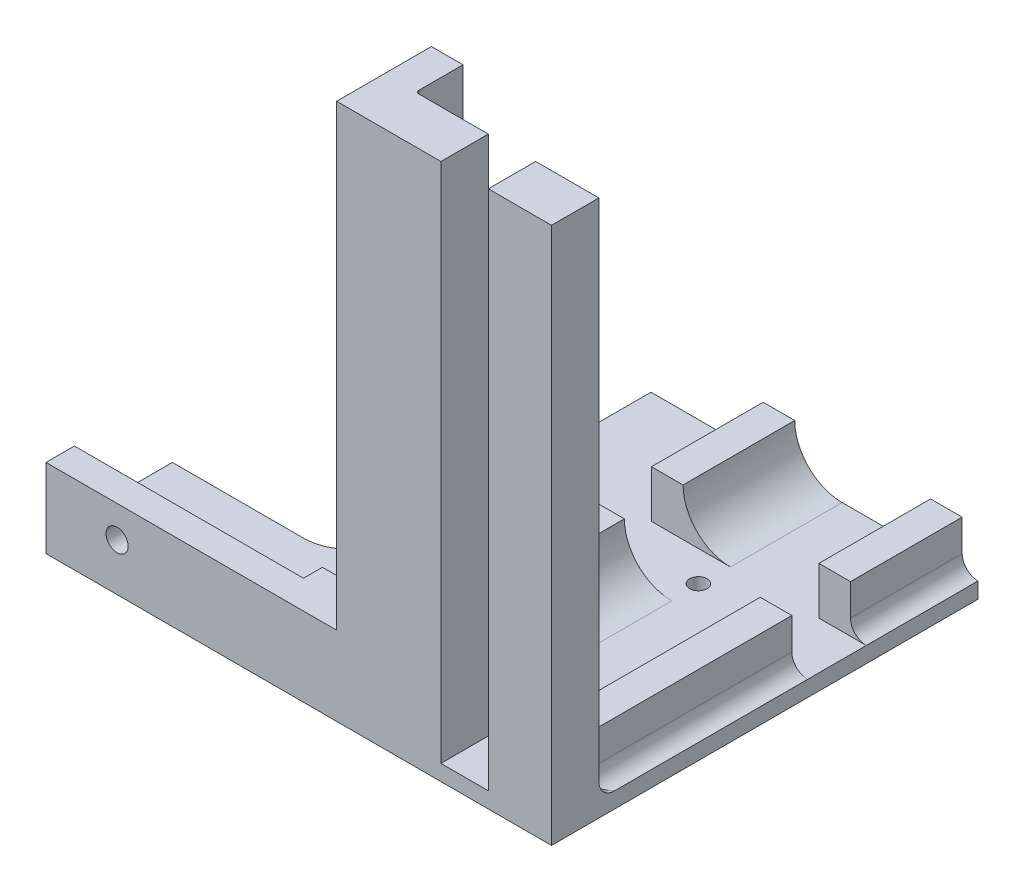
SolidWorks part; units mm, degrees
ref_plane "Front Plane" through (0, 0, 0) normal (0, 0, 1) x (1, 0, 0)
ref_plane "Top Plane" through (0, 0, 0) normal (0, 1, 0) x (1, 0, 0)
ref_plane "Right Plane" through (0, 0, 0) normal (1, 0, 0) x (0, 0, -1)
sketch "profile" plane through (0, 0, 0) normal (0, 0, 1) x (1, 0, 0)
  line L0 (11.8803, 7.4874) -> (14.5, 7.4874)
  line L1 (-5.5, 6.9749) -> (-7.8749, 4.6)
  line L2 (-7.8749, 4.6) -> (-12.1251, 4.6)
  line L3 (-12.1251, 4.6) -> (-14.5, 6.9749)
  line L4 (-8.1197, 7.4874) -> (-5.5, 7.4874)
  line L5 (-14.5, 6.9749) -> (-15.0126, 7.4874)
  line L6 (14.5, 6.9749) -> (12.1251, 4.6)
  line L7 (12.1251, 4.6) -> (7.8749, 4.6)
  line L8 (7.8749, 4.6) -> (5.5, 6.9749)
  line L9 (-14.7464, 10.3536) -> (-5.2536, 10.3536)
  line L10 (-14.5, 7.4874) -> (-11.8803, 7.4874)
  line L11 (5.5, 7.4874) -> (8.5334, 7.4874)
  line L12 (5.6673, 10.3536) -> (14.7464, 10.3536)
  line L13 (-15.0126, 7.4874) -> (-14.5, 7.4874)
  line L14 (-5.5, 6.9749) -> (-4.9874, 7.4874)
  line L15 (-4.9874, 7.4874) -> (-5.5, 7.4874)
  line L16 (5.5, 6.9749) -> (4.9874, 7.4874)
  line L17 (4.9874, 7.4874) -> (5.5, 7.4874)
  line L18 (14.5, 6.9749) -> (15.0126, 7.4874)
  line L19 (15.0126, 7.4874) -> (14.5, 7.4874)
  line L20 (-12.7464, 8.3536) -> (-14.7464, 10.3536)
  line L21 (-5.2536, 10.3536) -> (-7.2536, 8.3536)
  line L22 (7.6673, 8.3536) -> (5.6673, 10.3536)
  line L23 (14.7464, 10.3536) -> (12.7464, 8.3536)
  line L24 (-12.7464, 8.3536) -> (-11.8803, 7.4874)
  line L25 (-7.2536, 8.3536) -> (-8.1197, 7.4874)
  line L26 (7.6673, 8.3536) -> (8.5334, 7.4874)
  line L27 (12.7464, 8.3536) -> (11.8803, 7.4874)
  line L28 (-14.7464, 10.3536) -> (-20, 10.3536)
  line L29 (-20, 10.3536) -> (-20, 15.3536)
  line L30 (-20, 15.3536) -> (20, 15.3536)
  line L31 (20, 15.3536) -> (20, 10.3536)
  line L32 (20, 10.3536) -> (14.7464, 10.3536)
  line L33 (-5.2536, 10.3536) -> (5.6673, 10.3536)
  point P0 (-10, 4.6)
  point P1 (10, 4.6)
  dimension "D1" = 4.2503
  dimension "D2" = 5.7536
  dimension "D3" = 15.7497
  dimension "D4" = 20
  dimension "D5" = 5
extrude "Boss-Extrude1" add sketch "profile" along normal blind 250 contours L9 L33 L12 L32 L31 L30 L29 L28 region at (0, 12.8536, 0)
extrude "Boss-Extrude2" add sketch "Sketch1<3>" along normal blind 50 separate body contours L25 L21 L9 L20 L24 L10 L13 L5 L3 L2 L1 L14 L15 L4 | L27 L23 L12 L22 L26 L11 L17 L16 L8 L7 L6 L18 L19 L0 region at (10.0959, 7.5838, 0) region at (-10, 7.6238, 0)
sketch "Sketch1<3>" plane through (0, 0, 0) normal (0, 0, 1) x (1, 0, 0) same geometry as "profile"
pattern_linear "LPattern1" count 4 spacing 60 along (0, 0, 1) of "Boss-Extrude2"
sketch "Sketch2" plane through (0, 10.3536, 0) normal (0, -1, 0) x (1, 0, 0)
  line L0 (10, 250) -> (10, 0) construction
  line L1 (-20, 250) -> (20, 250) construction
  line L2 (12.1251, 0) -> (7.8749, 0) construction
  line L3 (-10, 230) -> (-10, 0) construction
  line L4 (-7.8749, 230) -> (-12.1251, 230) construction
  line L5 (-7.8749, 0) -> (-12.1251, 0) construction
  line L6 (-7.8749, 180) -> (-7.8749, 170) construction
  line L7 (-7.8749, 180) -> (-12.1251, 180) construction
  circle A0 centre (-10, 175) radius 2.75
  circle A1 centre (10, 175) radius 2.75
  circle A2 centre (-10, 115) radius 2.75
  circle A3 centre (10, 115) radius 2.75
  circle A4 centre (-10, 55) radius 2.75
  circle A5 centre (10, 55) radius 2.75
  point P21 (-7.8749, 175)
  dimension "D1" = 5.5
  dimension "D2" = 3
extrude "Cut-Extrude1" cut sketch "Sketch2" against normal through all
sketch "upper_acrylic_supp" plane through (0, 15.3536, 0) normal (0, 1, 0) x (1, 0, 0)
  line L0 (-20, 0) -> (20, 0) construction
  line L1 (-20, -250) -> (-34.5, -250) construction
  line L2 (-20, -250) -> (-20, 0) construction
  line L3 (-20, 0) -> (-34.5, 0) construction
  line L4 (-34.5, -250) -> (-34.5, 0) construction
  line L6 (-34.5, -250) -> (-24.5, -250)
  line L7 (-34.5, -250) -> (-34.5, -183.9264)
  line L8 (-34.5, -183.9264) -> (-24.5, -183.9264)
  line L9 (-24.5, -250) -> (-24.5, -183.9264)
  line L10 (-34.5, -165.3527) -> (-24.5, -165.3527)
  line L11 (-34.5, -165.3527) -> (-34.5, -123.8775)
  line L12 (-34.5, -123.8775) -> (-24.5, -123.8775)
  line L13 (-24.5, -165.3527) -> (-24.5, -123.8775)
  line L14 (-34.5, -106.5661) -> (-24.5, -106.5661)
  line L15 (-34.5, -106.5661) -> (-34.5, -64.0089)
  line L16 (-34.5, -64.0089) -> (-24.5, -64.0089)
  line L17 (-24.5, -106.5661) -> (-24.5, -64.0089)
  line L18 (-34.5, -45.5583) -> (-24.5, -45.5583)
  line L19 (-34.5, -45.5583) -> (-34.5, 0)
  line L20 (-34.5, 0) -> (-24.5, 0)
  line L21 (-24.5, -45.5583) -> (-24.5, 0)
  line L22 (-20, -250) -> (-40, -250)
  line L23 (-20, -250) -> (-20, 0)
  line L24 (-20, 0) -> (-40, 0)
  line L25 (-40, -250) -> (-40, 0)
  line M21 (-20, 0) -> (-20, -250)
  dimension "D1" = 5.5
  dimension "D2" = 10
  dimension "D3" = 20
extrude "Boss-Extrude3" add sketch "upper_acrylic_supp" against normal blind 5 contours L25 L22 L24 L21 L18 L19 L17 L14 L15 L16 L13 L10 L11 L12 L9 L6 L7 L8 M21 | L14 L17 L16 L15 | L10 L13 L12 L11 | L6 L9 L8 L7 | L18 L21 L20 L19 region at (-29.5, 15.3536, 216.9632) region at (-30.3215, 15.3536, 123.2164) region at (-29.5, 15.3536, 22.7792) region at (-29.5, 15.3536, 144.6151) region at (-29.5, 15.3536, 85.2875)
extrude "Boss-Extrude4" add sketch "upper_acrylic_supp<3>" along normal blind 15 contours L6 L9 L8 L7 | L10 L13 L12 L11 | L14 L17 L16 L15 | L18 L21 L20 L19 region at (-29.5, 15.3536, 216.9632) region at (-29.5, 15.3536, 22.7792) region at (-29.5, 15.3536, 144.6151) region at (-29.5, 15.3536, 85.2875)
sketch "upper_acrylic_supp<3>" plane through (0, 15.3536, 0) normal (0, 1, 0) x (1, 0, 0) same geometry as "upper_acrylic_supp"
fillet "Fillet1" radius 15 4 edges at (-24.5, 15.3536, 22.7792) (-24.5, 15.3536, 85.2875) (-24.5, 15.3536, 144.6151) (-24.5, 15.3536, 216.9632)
sketch "Sketch4" plane through (0, 15.3536, 0) normal (0, 1, 0) x (1, 0, 0)
  line L0 (20, -250) -> (20, 0) construction
  line L1 (-40, -250) -> (20, -250)
  line L2 (-40, -250) -> (-40, -265)
  line L3 (-40, -265) -> (20, -265)
  line L4 (20, -250) -> (20, -265)
  line L5 (-40, 0) -> (20, 0)
  line L6 (-40, 0) -> (-40, 15)
  line L7 (-40, 15) -> (20, 15)
  line L8 (20, 0) -> (20, 15)
  line L10 (-34.5, -265) -> (-34.5, 15) construction
  dimension "D1" = 15
  dimension "D2" = 15
extrude "Boss-Extrude5" add sketch "Sketch4" along normal mid plane 10
extrude "Boss-Extrude6" add sketch "Sketch4<3>" along normal blind 60
sketch "Sketch4<3>" plane through (0, 15.3536, 0) normal (0, 1, 0) x (1, 0, 0) same geometry as "Sketch4"
sketch "Sketch5" plane through (0, 0, 250) normal (0, 0, -1) x (-1, 0, 0)
  line L0 (-20, 75.3536) -> (40, 75.3536) construction
  line L1 (40, 15.3536) -> (34.5, 15.3536)
  line L2 (40, 15.3536) -> (40, 75.3536)
  line L3 (40, 75.3536) -> (34.5, 75.3536)
  line L4 (34.5, 15.3536) -> (34.5, 75.3536)
  line L6 (34.5, 15.3536) -> (24.5, 15.3536)
  line L7 (34.5, 15.3536) -> (34.5, 75.3536)
  line L8 (34.5, 75.3536) -> (24.5, 75.3536)
  line L9 (24.5, 15.3536) -> (24.5, 75.3536)
  line M5 (40, 75.3536) -> (-20, 75.3536)
  line M9 (24.5, 30.3536) -> (34.5, 30.3536)
  dimension "D1" = 5.5
  dimension "D2" = 10
extrude "Boss-Extrude7" add sketch "Sketch5" along normal blind 15 contours L9 L4 M9 M5 region at (-29.5, 52.8536, 250)
extrude "Boss-Extrude8" add sketch "Sketch5<3>" against normal blind 15 from surface contours L9 L4 M9 M5 region at (-29.5, 52.8536, 250) starting at face at (-18.2633, 33.7152, 0)
sketch "Sketch5<3>" plane through (0, 0, 250) normal (0, 0, -1) x (-1, 0, 0) same geometry as "Sketch5"
fillet "Fillet2" radius 1 6 edges at (5.25, 15.3536, 0) (-20.1066, 19.747, 0) (5.25, 15.3536, 250) (-20.1066, 19.747, 250) (-24.5, 52.8536, 0) (-24.5, 52.8536, 250)
sketch "Sketch6" plane through (-40, 0, 0) normal (-1, 0, 0) x (0, 0, 1)
  line L1 (250, 15.3536) -> (256, 15.3536)
  line L2 (250, 15.3536) -> (250, 75.3536)
  line L3 (250, 75.3536) -> (256, 75.3536)
  line L4 (256, 15.3536) -> (256, 75.3536)
  line L6 (0, 15.3536) -> (-6, 15.3536)
  line L7 (0, 15.3536) -> (0, 75.3536)
  line L8 (0, 75.3536) -> (-6, 75.3536)
  line L9 (-6, 15.3536) -> (-6, 75.3536)
  dimension "D1" = 6
  dimension "D2" = 6
extrude "Cut-Extrude2" cut sketch "Sketch6" against normal blind 6
sketch "Sketch7" plane through (-40, 0, 0) normal (-1, 0, 0) x (0, 0, 1)
  line L8 (265, 75.3536) -> (256, 75.3536)
  line L9 (256, 75.3536) -> (256, 15.3536)
  line L10 (256, 15.3536) -> (-6, 15.3536)
  line L11 (-6, 15.3536) -> (-6, 75.3536)
  line L12 (-6, 75.3536) -> (-15, 75.3536)
  line L13 (-15, 75.3536) -> (-15, 10.3536)
  line L14 (-15, 10.3536) -> (265, 10.3536)
  line L15 (265, 10.3536) -> (265, 75.3536)
  line L16 (265, 75.3536) -> (256, 75.3536)
  line L17 (256, 75.3536) -> (256, 15.3536)
  line L18 (256, 15.3536) -> (-6, 15.3536)
  line L19 (-6, 15.3536) -> (-6, 75.3536)
  line L20 (-6, 75.3536) -> (-15, 75.3536)
  line L21 (-15, 75.3536) -> (-15, 10.3536)
  line L22 (-15, 10.3536) -> (265, 10.3536)
  line L23 (265, 10.3536) -> (265, 75.3536)
  dimension "D1" = 0
extrude "Boss-Extrude9" add sketch "Sketch7" along normal blind 30
sketch "Sketch8" plane through (-70, 0, 0) normal (-1, 0, 0) x (0, 0, 1)
  line L0 (-15, 10.3536) -> (265, 10.3536) construction
  line L1 (-44.3745, 35.3536) -> (289.2282, 35.3536)
  line L2 (-44.3745, 35.3536) -> (-44.3745, 94.3849)
  line L3 (-44.3745, 94.3849) -> (289.2282, 94.3849)
  line L4 (289.2282, 35.3536) -> (289.2282, 94.3849)
  dimension "D1" = 25
extrude "Cut-Extrude3" cut sketch "Sketch8" against normal blind 150
sketch "Sketch9" plane through (-34, 0, 0) normal (-1, 0, 0) x (0, 0, 1)
  line L4 (256, 15.3536) -> (256, 35.3536)
  line L5 (256, 35.3536) -> (250, 35.3536)
  line L6 (250, 35.3536) -> (250, 15.3536)
  line L7 (250, 15.3536) -> (256, 15.3536)
  line L8 (256, 15.3536) -> (256, 35.3536)
  line L9 (256, 35.3536) -> (250, 35.3536)
  line L10 (250, 35.3536) -> (250, 15.3536)
  line L11 (250, 15.3536) -> (256, 15.3536)
  line L12 (0, 35.3536) -> (-6, 35.3536)
  line L13 (-6, 35.3536) -> (-6, 15.3536)
  line L14 (-6, 15.3536) -> (0, 15.3536)
  line L15 (0, 15.3536) -> (0, 35.3536)
  line L16 (0, 35.3536) -> (-6, 35.3536)
  line L17 (-6, 35.3536) -> (-6, 15.3536)
  line L18 (-6, 15.3536) -> (0, 15.3536)
  line L19 (0, 15.3536) -> (0, 35.3536)
  dimension "D1" = 0
  dimension "D2" = 0
extrude "cloth_escape_gap" add sketch "Sketch9" along normal blind 20
sketch "Sketch11" plane through (-70, 0, 0) normal (-1, 0, 0) x (0, 0, 1)
  line L0 (256, 35.3536) -> (256, 15.3536) construction
  line L1 (-15, 35.3536) -> (-6, 35.3536)
  line L2 (-15, 35.3536) -> (-15, 15.3536)
  line L3 (-15, 15.3536) -> (-6, 15.3536)
  line L4 (-6, 35.3536) -> (-6, 15.3536)
  line L5 (265, 35.3536) -> (256, 35.3536)
  line L6 (265, 35.3536) -> (265, 15.3536)
  line L7 (265, 15.3536) -> (256, 15.3536)
  line L8 (256, 35.3536) -> (256, 15.3536)
  line L9 (256, 15.3536) -> (256, 35.3536) construction
extrude "Boss-Extrude11" add sketch "Sketch11" along normal blind 100
sketch "Sketch12" plane through (0, 10.3536, 0) normal (0, -1, 0) x (1, 0, 0)
  line L0 (-70, -15) -> (-170, -10.5)
  line L1 (-170, -15) -> (-170, -6) construction
  line L2 (-170, -10.5) -> (-170, -15)
  line L3 (-170, -15) -> (-70, -15) construction
  line L4 (-170, -15) -> (-70, -15)
  line L5 (-70, 265) -> (-170, 260.5)
  line L6 (-170, 256) -> (-170, 265) construction
  line L7 (-170, 260.5) -> (-170, 265)
  line L8 (-170, 265) -> (-70, 265)
extrude "Cut-Extrude4" cut sketch "Sketch12" against normal blind 68 contours L8 L7 L5 | L0 L2 L4 region at (-136.6667, 10.3536, 263.5)
sketch "Sketch13" plane through (-70, 0, 0) normal (-1, 0, 0) x (0, 0, 1)
  line L0 (256, 15.3536) -> (265, 15.3536) construction
  line L1 (-15, 10.3536) -> (25, 10.3536)
  line L2 (-15, 10.3536) -> (-15, 15.3536)
  line L3 (-15, 15.3536) -> (25, 15.3536)
  line L4 (25, 10.3536) -> (25, 15.3536)
  line L5 (265, 10.3536) -> (225, 10.3536)
  line L6 (265, 10.3536) -> (265, 15.3536)
  line L7 (265, 15.3536) -> (225, 15.3536)
  line L8 (225, 10.3536) -> (225, 15.3536)
  line L9 (256, 15.3536) -> (-6, 15.3536) construction
  dimension "D1" = 40
  dimension "D2" = 40
extrude "Boss-Extrude13" add sketch "Sketch13" along normal blind 100
sketch "Sketch14" plane through (0, 15.3536, 0) normal (0, 1, 0) x (1, 0, 0)
  line L3 (-70, -265) -> (-170, -260.5)
  line L4 (-170, -260.5) -> (-170, -265)
  line L5 (-170, -265) -> (-70, -265)
  line L6 (-70, -265) -> (-170, -260.5)
  line L7 (-170, -260.5) -> (-170, -265)
  line L8 (-170, -265) -> (-70, -265)
  line L9 (-170, 15) -> (-170, 10.5)
  line L10 (-170, 10.5) -> (-70, 15)
  line L11 (-70, 15) -> (-170, 15)
  line L12 (-170, 15) -> (-170, 10.5)
  line L13 (-170, 10.5) -> (-70, 15)
  line L14 (-70, 15) -> (-170, 15)
  dimension "D1" = 0
  dimension "D2" = 0
extrude "Cut-Extrude5" cut sketch "Sketch14" against normal blind 100
fillet "Fillet3" radius 15 2 edges at (-70, 12.8536, 25) (-70, 12.8536, 225)
sketch "Sketch16" plane through (0, 15.3536, 0) normal (0, 1, 0) x (1, 0, 0)
  line L0 (20, -1) -> (-9.5, -1) construction
  line L1 (-34.5, -235) -> (18.5, -235) construction
  line L2 (-34.5, -235) -> (-34.5, -1) construction
  line L3 (-34.5, -1) -> (18.5, -1) construction
  line L4 (18.5, -235) -> (18.5, -1) construction
  line L5 (20, -265) -> (-70, -265) construction
  line L6 (18.5, -265) -> (33.5, -265)
  line L7 (18.5, -265) -> (18.5, 15)
  line L8 (18.5, 15) -> (33.5, 15)
  line L9 (33.5, -265) -> (33.5, 15)
  line L10 (-70, 15) -> (20, 15) construction
  line L11 (18.5, -250) -> (33.5, -250)
  line L12 (18.5, 0) -> (33.5, 0)
  line L13 (-23.5, -250) -> (20, -250) construction
  line L14 (-9.5, 0) -> (20, 0) construction
  line L15 (18.5, -250) -> (28.5, -250)
  line L16 (28.5, -250) -> (28.5, -183.9264)
  line L17 (28.5, 0) -> (18.5, 0)
  line L18 (18.5, -183.9264) -> (28.5, -183.9264)
  line L19 (18.5, -165.3527) -> (28.5, -165.3527)
  line L20 (18.5, -123.8775) -> (28.5, -123.8775)
  line L21 (18.5, -106.5661) -> (28.5, -106.5661)
  line L22 (18.5, -64.0089) -> (28.5, -64.0089)
  line L23 (18.5, -43.1778) -> (28.5, -43.1778)
  line L24 (-34.5, -165.3527) -> (-9.5, -165.3527) construction
  line L25 (-34.5, -183.9264) -> (-9.5, -183.9264) construction
  line L26 (-34.5, -106.5661) -> (-9.5, -106.5661) construction
  line L27 (-34.5, -123.8775) -> (-9.5, -123.8775) construction
  line L28 (-9.5, -64.0089) -> (-24.5, -64.0089) construction
  line L30 (28.5, -165.3527) -> (28.5, -123.8775)
  line L31 (28.5, -106.5661) -> (28.5, -64.0089)
  line L32 (28.5, -43.1778) -> (28.5, 0)
  line M38 (-9.5, -249) -> (20, -249)
  line M39 (20, -249) -> (20, -1)
  line M40 (20, -1) -> (-9.5, -1)
  dimension "D1" = 53
  dimension "D2" = 15
  dimension "D3" = 10
extrude "Boss-Extrude14" add sketch "Sketch16" along direction (0, -1, 0) on the side of the normal up to surface (20 mm away) from surface contours L7 L12 L9 L8 | L11 L7 L6 L9 region at (26, 15.3536, 257.5) region at (26, 15.3536, -7.5) up to face at (-51.6423, 35.3536, 251.8089) starting at face at (-10, 10.3536, 25)
extrude "Cut-Extrude6" cut sketch "Sketch16<5>" against normal blind 10 and the other way blind 30 contours L11 L7 L6 L9 | L32 L23 L22 L31 L21 L20 L30 L19 L18 L16 L11 L9 L12 M39 | L19 L30 L20 M39 | L21 L31 L22 M39 | L23 L32 L12 L7 M40 M39 | L7 L12 L9 L8 | L7 L23 M39 M40 | L23 L7 L22 M39 | L22 L7 L21 M39 | L21 L7 L20 M39 | L20 L7 L19 M39 | L19 L7 L18 M39 | L18 L7 M38 M39 | L18 L7 L11 L16 M39 M38 region at (26, 15.3536, 257.5) region at (24.2367, 15.3536, 217.0499) region at (29.1213, 15.3536, 121.3942) region at (19.25, 15.3536, 216.4632) region at (26, 15.3536, -7.5) region at (19.25, 15.3536, 174.6396) region at (24.2296, 15.3536, 21.5031) region at (19.25, 15.3536, 144.6151) region at (19.25, 15.3536, 115.2218) region at (24.25, 15.3536, 144.6151) region at (19.25, 15.3536, 22.0889) region at (19.25, 15.3536, 53.5934) region at (19.25, 15.3536, 85.2875) region at (24.25, 15.3536, 85.2875)
sketch "Sketch16<5>" plane through (0, 15.3536, 0) normal (0, 1, 0) x (1, 0, 0) same geometry as "Sketch16"
extrude "Boss-Extrude15" add sketch "Sketch16<6>" against normal up to surface (5 mm away) contours L32 L23 L22 L31 L21 L20 L30 L19 L18 L16 L11 L9 L12 M39 | L18 L7 L11 L16 M39 M38 | L11 L7 L6 L9 | L19 L30 L20 M39 | L21 L31 L22 M39 | L23 L32 L12 L7 M40 M39 | L7 L12 L9 L8 | L7 L23 M39 M40 | L23 L7 L22 M39 | L22 L7 L21 M39 | L21 L7 L20 M39 | L20 L7 L19 M39 | L19 L7 L18 M39 | L18 L7 M38 M39 region at (26, 15.3536, 257.5) region at (24.2367, 15.3536, 217.0499) region at (29.1213, 15.3536, 121.3942) region at (19.25, 15.3536, 216.4632) region at (26, 15.3536, -7.5) region at (19.25, 15.3536, 174.6396) region at (24.2296, 15.3536, 21.5031) region at (19.25, 15.3536, 144.6151) region at (19.25, 15.3536, 115.2218) region at (24.25, 15.3536, 144.6151) region at (19.25, 15.3536, 22.0889) region at (19.25, 15.3536, 53.5934) region at (19.25, 15.3536, 85.2875) region at (24.25, 15.3536, 85.2875) up to face at (-90.5656, 10.3536, 125)
sketch "Sketch16<6>" plane through (0, 15.3536, 0) normal (0, 1, 0) x (1, 0, 0) same geometry as "Sketch16"
extrude "Boss-Extrude16" add sketch "Sketch16<7>" along normal up to surface (20 mm away) contours L11 L7 L6 L9 | L7 L12 L9 L8 region at (26, 15.3536, 257.5) region at (26, 15.3536, -7.5) up to face at (-51.8923, 35.3536, 251.8089)
sketch "Sketch16<7>" plane through (0, 15.3536, 0) normal (0, 1, 0) x (1, 0, 0) same geometry as "Sketch16"
extrude "Boss-Extrude17" add sketch "Sketch16<8>" along normal up to surface (15 mm away) contours L18 L7 L11 L16 M39 M38 | L19 L30 L20 M39 | L21 L31 L22 M39 | L23 L32 L12 L7 M40 M39 | L7 L23 M39 M40 | L22 L7 L21 M39 | L20 L7 L19 M39 | L18 L7 M38 M39 region at (24.2367, 15.3536, 217.0499) region at (19.25, 15.3536, 216.4632) region at (24.2296, 15.3536, 21.5031) region at (19.25, 15.3536, 144.6151) region at (24.25, 15.3536, 144.6151) region at (19.25, 15.3536, 22.0889) region at (19.25, 15.3536, 85.2875) region at (24.25, 15.3536, 85.2875) up to face at (-29.5, 30.3536, 209.4632)
sketch "Sketch16<8>" plane through (0, 15.3536, 0) normal (0, 1, 0) x (1, 0, 0) same geometry as "Sketch16"
extrude "Boss-Extrude18" add sketch "Sketch14<2>" along normal up to surface (20 mm away) and the other way up to surface (5 mm away) up to face at (-49.3923, 35.3536, -1.8089) other way up to face at (-88.0656, 10.3536, 125)
sketch "Sketch14<2>" plane through (0, 15.3536, 0) normal (0, 1, 0) x (1, 0, 0) same geometry as "Sketch14"
fillet "Fillet4" radius 5 6 edges at (31, 15.3536, 250) (31, 15.3536, 0) (28.5, 15.3536, 21.5889) (28.5, 15.3536, 85.2875) (28.5, 15.3536, 144.6151) (28.5, 15.3536, 216.9632)
sketch "Sketch18" plane through (0, 35.3536, 0) normal (0, 1, 0) x (1, 0, 0)
  line L2 (-34.5, -250) -> (-34.5, -265)
  line L3 (-34.5, 15) -> (-34.5, 0)
  line L12 (-23.5, 0) -> (33.5, 0)
  line L13 (33.5, 0) -> (33.5, 15)
  line L14 (33.5, 15) -> (-170, 15)
  line L15 (-170, 15) -> (-170, 6)
  line L30 (-170, 6) -> (-54, 6)
  line L32 (-54, 6) -> (-54, 0)
  line L38 (-54, 0) -> (-34.5, 0)
  line L39 (-34.5, 0) -> (-34.5, -15)
  line L50 (-34.5, -15) -> (-24.5, -15)
  line L51 (-24.5, -15) -> (-24.5, -1)
  line L52 (-23.5, 0) -> (33.5, 0)
  line L53 (33.5, 0) -> (33.5, 15)
  line L54 (33.5, 15) -> (-34.5, 15)
  line L59 (-34.5, 0) -> (-34.5, -15)
  line L60 (-34.5, -15) -> (-24.5, -15)
  line L61 (-24.5, -15) -> (-24.5, -1)
  line L62 (-170, -265) -> (33.5, -265)
  line L63 (33.5, -265) -> (33.5, -250)
  line L64 (33.5, -250) -> (-23.5, -250)
  line L65 (-24.5, -249) -> (-24.5, -235)
  line L66 (-24.5, -235) -> (-34.5, -235)
  line L67 (-34.5, -235) -> (-34.5, -250)
  line L68 (-34.5, -250) -> (-54, -250)
  line L69 (-54, -250) -> (-54, -256)
  line L70 (-54, -256) -> (-170, -256)
  line L71 (-170, -256) -> (-170, -265)
  line L72 (-34.5, -265) -> (33.5, -265)
  line L73 (33.5, -265) -> (33.5, -250)
  line L74 (33.5, -250) -> (-23.5, -250)
  line L75 (-24.5, -249) -> (-24.5, -235)
  line L76 (-24.5, -235) -> (-34.5, -235)
  line L77 (-34.5, -235) -> (-34.5, -250)
  arc A5 (-23.5, 0) -> (-24.5, -1) centre (-23.5, -1) ccw
  arc A6 (-23.5, 0) -> (-24.5, -1) centre (-23.5, -1) ccw
  arc A7 (-24.5, -249) -> (-23.5, -250) centre (-23.5, -249) ccw
  arc A8 (-24.5, -249) -> (-23.5, -250) centre (-23.5, -249) ccw
  dimension "D1" = 0
  dimension "D2" = 0
extrude "Boss-Extrude21" add sketch "Sketch18" along normal blind 170 from surface starting at face at (-91.6787, 10.3536, 125)
sketch "Sketch19" plane through (0, 15.3536, 0) normal (0, 1, 0) x (1, 0, 0)
  line L0 (-170, -25) -> (-170, 6) construction
  line L1 (-70, -125) -> (-196.5165, -125) construction
  line L2 (-70, -210) -> (-70, -40) construction
  circle A0 centre (-154, -9.5) radius 3.5
  circle A1 centre (-104, -9.5) radius 3.5
  circle A2 centre (-104, -240.5) radius 3.5
  circle A3 centre (-154, -240.5) radius 3.5
  point P6 (-170, -9.5)
  dimension "D1" = 7
  dimension "D2" = 50
  dimension "D3" = 50
extrude "Cut-Extrude7" cut sketch "Sketch19" against normal blind 10
sketch "Sketch20" plane through (0, 0, 256) normal (0, 0, -1) x (-1, 0, 0)
  line L4 (34.5, 35.3536) -> (34.5, 15.3536)
  line L5 (34.5, 15.3536) -> (54, 15.3536)
  line L6 (54, 15.3536) -> (54, 35.3536)
  line L7 (54, 35.3536) -> (34.5, 35.3536)
  line L8 (34.5, 35.3536) -> (34.5, 15.3536)
  line L9 (34.5, 15.3536) -> (54, 15.3536)
  line L10 (54, 15.3536) -> (54, 35.3536)
  line L11 (54, 35.3536) -> (34.5, 35.3536)
  circle A0 centre (104, 25.3536) radius 3.5
  circle A1 centre (154, 25.3536) radius 3.5
  point P8 (54, 25.3536)
  dimension "D3" = 7
  dimension "D2" = 50
  dimension "D4" = 50
  dimension "D1" = 0
extrude "Cut-Extrude8" cut sketch "Sketch20" against normal blind 10 and the other way blind 355 contours A0 | A1 region at (-104, 25.3536, 256) region at (-154, 25.3536, 256)
sketch "Sketch21" plane through (0, 0, 0) normal (0, 0, 1) x (1, 0, 0)
  line L1 (13.5, 15.3536) -> (-1.5, 15.3536)
  line L2 (13.5, 15.3536) -> (13.5, 212.8546)
  line L3 (13.5, 212.8546) -> (-1.5, 212.8546)
  line L4 (-1.5, 15.3536) -> (-1.5, 212.8546)
  line L6 (18.5, 15.3536) -> (-9.5, 15.3536) construction
  line L7 (18.5, 30.3536) -> (18.5, 16.3536) construction
  dimension "D1" = 15
  dimension "D2" = 5
extrude "Cut-Extrude9" cut sketch "Sketch21" along normal blind 340
sketch "Sketch22" plane through (0, 0, 0) normal (0, 1, 0) x (1, 0, 0)
  line L0 (33.5, 15) -> (-34.5, 15) construction
  line L5 (33.5, 15) -> (-126.5, 15)
  line L6 (33.5, 15) -> (33.5, -120)
  line L7 (33.5, -120) -> (-126.5, -120)
  line L8 (-126.5, 15) -> (-126.5, -120)
  line L9 (33.5, 0) -> (33.5, 15) construction
  line L10 (33.5, -265) -> (33.5, -250) construction
  line L11 (33.5, -265) -> (-126.5, -265)
  line L12 (33.5, -265) -> (33.5, -130)
  line L13 (33.5, -130) -> (-126.5, -130)
  line L14 (-126.5, -265) -> (-126.5, -130)
  line L15 (-126.5, -120) -> (-126.5, -130)
  line L16 (33.5, -120) -> (33.5, -130)
  line L17 (-34.5, -265) -> (-170, -265) construction
  line L19 (-126.5, 15) -> (-186.5, 15)
  line L20 (-126.5, 15) -> (-126.5, -265)
  line L21 (-126.5, -265) -> (-186.5, -265)
  line L22 (-186.5, 15) -> (-186.5, -265)
  dimension "D1" = 160
  dimension "D2" = 135
  dimension "D3" = 135
  dimension "D4" = 60
extrude "Cut-Extrude11" cut sketch "Sketch22" along normal blind 217 contours L19 L22 L21 L14 L15 L8 | L16 L7 L15 L13 | L5 L8 L7 L6 region at (-46.5, 0, 52.5) region at (-156.5, 0, 125) region at (-46.5, 0, 125)
